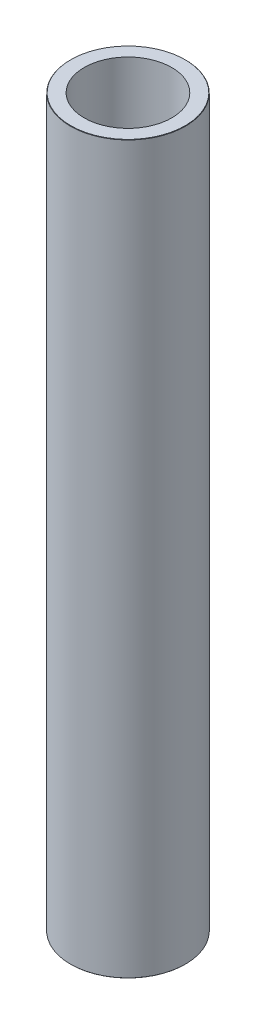
SolidWorks part; units mm, degrees
ref_plane "Front Plane" through (0, 0, 0) normal (0, 0, 1) x (1, 0, 0)
ref_plane "Top Plane" through (0, 0, 0) normal (0, 1, 0) x (1, 0, 0)
ref_plane "Right Plane" through (0, 0, 0) normal (1, 0, 0) x (0, 0, -1)
sketch "Sketch1" plane through (0, 0, 0) normal (0, 1, 0) x (1, 0, 0)
  circle A0 centre (0, 0) radius 47.5
  dimension "SHAFT_OD" = 95
extrude "Boss-Extrude1" add sketch "Sketch1" along normal blind 600
sketch "Sketch2" plane through (0, 0, 0) normal (0, 1, 0) x (1, 0, 0)
  circle A0 centre (0, 0) radius 36.1367
  dimension "BORE_D" = 72.2734
extrude "Cut-Extrude1" cut sketch "Sketch2" along normal through all
chamfer "Chamfer1" distance 0.2511 angle 45 2 edges at (0, 600, 47.5) (0, 0, 47.5)
